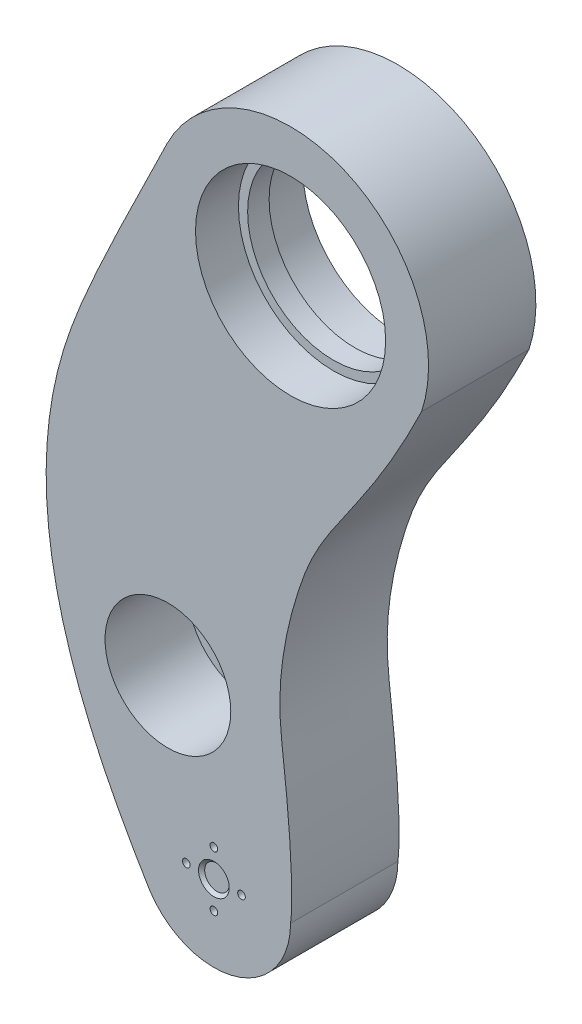
SolidWorks part; units mm, degrees
ref_plane "Ebene vorne" through (0, 0, 0) normal (0, 0, 1) x (1, 0, 0)
ref_plane "Ebene oben" through (0, 0, 0) normal (0, 1, 0) x (1, 0, 0)
ref_plane "Ebene rechts" through (0, 0, 0) normal (1, 0, 0) x (0, 0, -1)
sketch "Skizze1" plane through (0, 0, 0) normal (0, 0, 1) x (1, 0, 0)
  circle A0 centre (0, 0) radius 9
  circle A6 centre (0, 0) radius 25
  circle A7 centre (25, 180) radius 45
  circle A8 centre (25, 180) radius 28
  spline S0 degree 3 poles (-15.2208, 200.1813) (-37.2573, 155.4099) (-73.4434, 79.5174) (-38.6711, 15.7685) (-20.9233, -13.6827) knots 0 0 0 0 0.231883 1 1 1 1
  spline S1 degree 3 poles (67.7341, 165.9004) (51.1385, 131.5089) (36.2521, 119.622) (25.0061, 88.4676) (20.0361, 66.2697) (25.6637, 21.506) (25.7093, 4.904) (25, 0) knots 0 0 0 0 0.347734 0.409135 0.591244 0.652607 1 1 1 1
  point P14 (0, 0)
  dimension "D1" = 18
  dimension "D3" = 50
  dimension "D5" = 90
  dimension "D7" = 56
  dimension "D4" = 180
  dimension "D6" = 25
extrude "Aufsatz-Linear austragen1" add sketch "Skizze1" along normal blind 35 contours S1 A7 S0 | S1 A7 S0 A6 | A6 S0 A0 | A0 region at (0, 0, 0) region at (-20.8092, -12.5008, 0) region at (-11.7098, 87.9057, 0) region at (2.5666, 142.4659, 0)
sketch "Skizze2" plane through (0, 0, 35) normal (0, 0, 1) x (1, 0, 0)
  circle A0 centre (0, 0) radius 4
  dimension "D1" = 8
extrude "Schnitt-Linear austragen1" cut sketch "Skizze2" against normal blind 1 contours A0
chamfer "Fase1" distance 1 angle 45 1 edges at (4, 0, 35)
sketch "Skizze3" plane through (0, 0, 35) normal (0, 0, 1) x (1, 0, 0)
sketch "Skizze4" plane through (0, 0, 35) normal (0, 0, 1) x (1, 0, 0)
  arc A0 (-1.247, 8.9132) -> (-8.9132, 1.247) centre (0, 0) ccw
  circle A1 centre (9, 0) radius 1.25
  circle A2 centre (0, -9) radius 1.25
  circle A3 centre (-9, 0) radius 1.25
  circle A4 centre (0, 9) radius 1.25
  arc A5 (-8.9132, -1.247) -> (-1.247, -8.9132) centre (0, 0) ccw
  arc A6 (8.9132, 1.247) -> (1.247, 8.9132) centre (0, 0) ccw
  arc A7 (1.247, -8.9132) -> (8.9132, -1.247) centre (0, 0) ccw
  point P14 (0, 0)
  dimension "D1" = 18
  dimension "D2" = 4
  dimension "D3" = 2.5
extrude "Schnitt-Linear austragen2" cut sketch "Skizze4" against normal blind 15 contours A4 | A1 | A2 | A3 region at (0, 9, 35) region at (-9, 0, 35) region at (9, 0, 35) region at (0, -9, 35)
sketch "Skizze5" plane through (0, 0, 0) normal (0, 0, -1) x (-1, 0, 0)
  circle A0 centre (0, 0) radius 8
  circle A1 centre (8, 0) radius 1.25
  circle A2 centre (0, -8) radius 1.25
  circle A3 centre (-8, 0) radius 1.25
  circle A4 centre (0, 8) radius 1.25
  circle A5 centre (0, 0) radius 9.25
  point P14 (0, 0)
  dimension "D1" = 4
  dimension "D3" = 16
extrude "Schnitt-Linear austragen3" cut sketch "Skizze5" against normal blind 15 contours A0 A4 | A0 A4 | A0 A3 | A0 A3 | A0 A1 | A0 A1 | A0 A2 | A0 A2 region at (-7.4523, 0, 0) region at (-8.5125, 0, 0) region at (0, 7.4523, 0) region at (0, 8.5125, 0) region at (0, -8.5125, 0) region at (0, -7.4523, 0) region at (7.4523, 0, 0) region at (8.5125, 0, 0)
sketch "Skizze6" plane through (0, 0, 35) normal (0, 0, 1) x (1, 0, 0)
  line L0 (-49.7352, 50) -> (22.1206, 50) construction
  circle A1 centre (-15, 50) radius 12.5
  spline S0 degree 3 poles (-15.2208, 200.1813) (-37.2573, 155.4099) (-73.4434, 79.5174) (-38.6711, 15.7685) (-20.9233, -13.6827) knots 0 0 0 0 0.231883 1 1 1 1 construction
  spline S1 degree 3 poles (67.7341, 165.9004) (51.1385, 131.5089) (36.2521, 119.622) (25.0061, 88.4676) (20.0361, 66.2697) (25.6637, 21.506) (25.7093, 4.904) (25, 0) knots 0 0 0 0 0.347734 0.409135 0.591244 0.652607 1 1 1 1 construction
  dimension "D1" = 50
  dimension "D2" = 25
  dimension "D3" = 15
extrude "Schnitt-Linear austragen4" cut sketch "Skizze6" against normal blind 35
sketch "Skizze7" plane through (0, 0, 35) normal (0, 0, 1) x (1, 0, 0)
  circle A0 centre (-15, 50) radius 20.5
  dimension "D1" = 41
extrude "Schnitt-Linear austragen5" cut sketch "Skizze7" against normal offset from surface (27 mm away) 8 up to face at (-2.5, 50, 0)
sketch "Skizze8" plane through (0, 0, 8) normal (0, 0, 1) x (1, 0, 0)
  line L0 (-15, 50) -> (-13.8879, 32.5354) construction
  arc A0 (-18.0975, 67.2237) -> (-32.4775, 50.8878) centre (-15, 50) ccw
  circle A1 centre (-13.8879, 32.5354) radius 2
  circle A2 centre (-32.4646, 48.8879) radius 2
  circle A3 centre (-16.1121, 67.4646) radius 2
  circle A4 centre (2.4646, 51.1121) radius 2
  arc A5 (2.2237, 53.0975) -> (-14.1122, 67.4775) centre (-15, 50) ccw
  arc A6 (-11.9025, 32.7763) -> (2.2237, 53.0975) centre (-15, 50) ccw
  arc A7 (-32.4775, 50.8878) -> (-15.8878, 32.5225) centre (-15, 50) ccw
  point P14 (-15, 50)
  dimension "D1" = 4
  dimension "D2" = 4
  dimension "D3" = 17.5
extrude "Schnitt-Linear austragen6" cut sketch "Skizze8" against normal blind 15 contours A4 | A3 | A1 | A2 | A2 | A4 region at (-16.1121, 67.4646, 8) region at (-31.5973, 48.9431, 8) region at (1.5973, 51.0569, 8) region at (-13.8879, 32.5354, 8)
sketch "Skizze9" plane through (0, 0, 0) normal (0, 0, -1) x (-1, 0, 0)
  circle A0 centre (13.8879, 32.5354) radius 3.5
  circle A1 centre (-2.4646, 51.1121) radius 3.5
  circle A2 centre (16.1121, 67.4646) radius 3.5
  circle A3 centre (32.4646, 48.8879) radius 3.5
  point P3 (15, 50)
  point P14 (15, 50)
  dimension "D1" = 7
  dimension "D2" = 4
extrude "Schnitt-Linear austragen7" cut sketch "Skizze9" against normal blind 4
sketch "Skizze10" plane through (0, 0, 35) normal (0, 0, 1) x (1, 0, 0)
  circle A0 centre (25, 180) radius 31
  dimension "D1" = 62
extrude "Schnitt-Linear austragen8" cut sketch "Skizze10" against normal blind 14
ref_plane "Ebene1" through (0, 0, 17.5) normal (0, 0, 1) x (1, 0, 0)
mirror "Spiegeln1" about plane through (0, 0, 17.5) normal (0, 0, 1) of "Schnitt-Linear austragen8"
sketch "Skizze11" plane through (0, 0, 0) normal (0, 0, 1) x (1, 0, 0)
  circle A0 centre (12.8689, 101.3867) radius 1.65
extrude "Schnitt-Linear austragen10" cut sketch "Skizze11" along normal blind 15
sketch "Skizze12" plane through (0, 0, 0) normal (0, 0, -1) x (-1, 0, 0)
  line L1 (-2, 140) -> (-25, 180) construction
  circle A0 centre (-2, 140) radius 2.1
  circle A1 centre (-25, 180) radius 32
  circle A2 centre (-2, 140) radius 7.5
  circle A3 centre (-25, 180) radius 28 construction
  point P9 (4.2687, 139.7406)
  dimension "D1" = 4.2
  dimension "D2" = 15
  dimension "D3" = 64
  dimension "D4" = 40
  dimension "D5" = 23
extrude "Schnitt-Linear austragen11" cut sketch "Skizze12" against normal blind 15 contours A0 region at (2, 140, 0)
